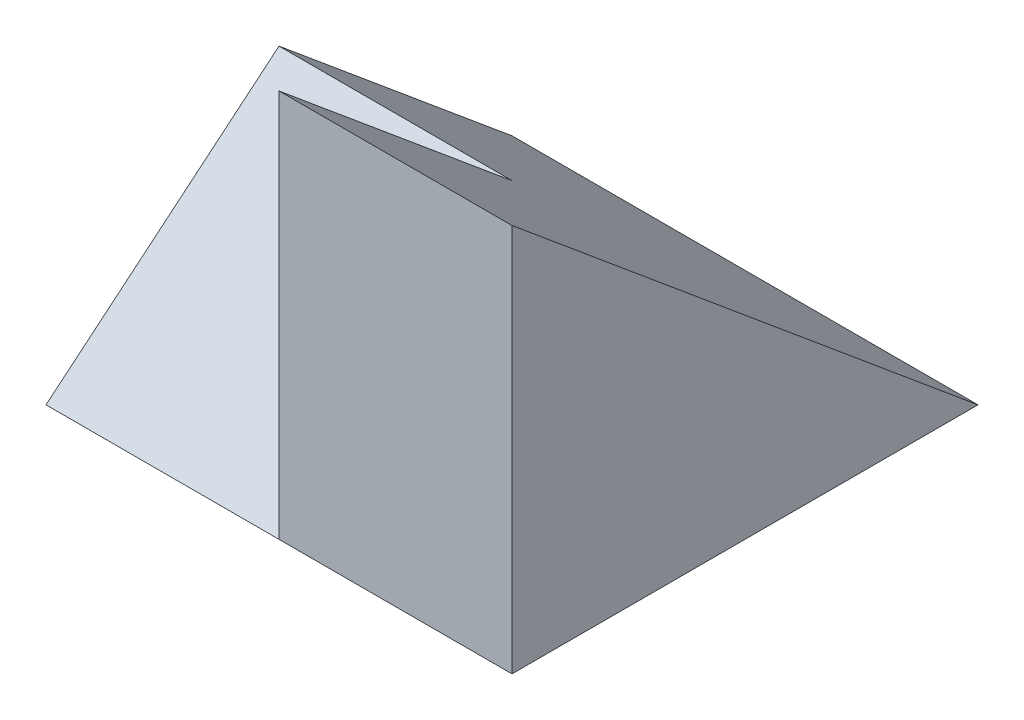
SolidWorks part; units mm, degrees
ref_plane "Front" through (0, 0, 0) normal (0, 0, 1) x (1, 0, 0)
ref_plane "Top" through (0, 0, 0) normal (0, 1, 0) x (1, 0, 0)
ref_plane "Right" through (0, 0, 0) normal (1, 0, 0) x (0, 0, -1)
sketch "Sketch1" plane through (0, 0, 0) normal (0, 1, 0) x (1, 0, 0)
  line L1 (-3, -3) -> (3, -3)
  line L2 (-3, -3) -> (-3, 3)
  line L3 (-3, 3) -> (3, 3)
  line L4 (3, -3) -> (3, 3)
  line L5 (-3, -3) -> (3, 3) construction
  line L6 (-3, 3) -> (3, -3) construction
  point P0 (0, 0)
  dimension "D1" = 6
  dimension "D2" = 6
extrude "Boss-Extrude1" add sketch "Sketch1" along normal blind 5
sketch "Sketch12" plane through (-3, 0, 0) normal (-1, 0, 0) x (0, 0, 1)
  line L0 (-3, 0) -> (3, 5)
  line L4 (-3, 0) -> (3, 0)
  line L5 (3, 0) -> (3, 5)
  line L6 (3, 5) -> (-3, 5)
  line L7 (-3, 5) -> (-3, 0)
  line L8 (-3, 0) -> (3, 0)
  line L9 (3, 0) -> (3, 5)
  line L10 (3, 5) -> (-3, 5)
  line L11 (-3, 5) -> (-3, 0)
  line M7 (3, 5) -> (-3, 5)
  line M8 (-3, 5) -> (-3, 0)
  dimension "D1" = 0
extrude "Cut-Extrude9" cut sketch "Sketch12" against normal blind 23.5 contours L0 M8 M7 region at (-3, 3.3333, -1)
sketch "Sketch13" plane through (-3, 0, 0) normal (-1, 0, 0) x (0, 0, 1)
  line L1 (0, 2.5) -> (3, 0)
  line L3 (3, 0) -> (3, 5)
  line L4 (3, 5) -> (-3, 0)
  line L5 (-3, 0) -> (3, 0)
  line L6 (3, 0) -> (3, 5)
  line L7 (3, 5) -> (-3, 0)
  line L8 (-3, 0) -> (3, 0)
  line M4 (3, 0) -> (3, 5)
  line M5 (3, 5) -> (-3, 0)
  dimension "D1" = 0
extrude "Cut-Extrude10" cut sketch "Sketch13" against normal blind 3 contours M5 M4 region at (-3, 2.5, 2)
